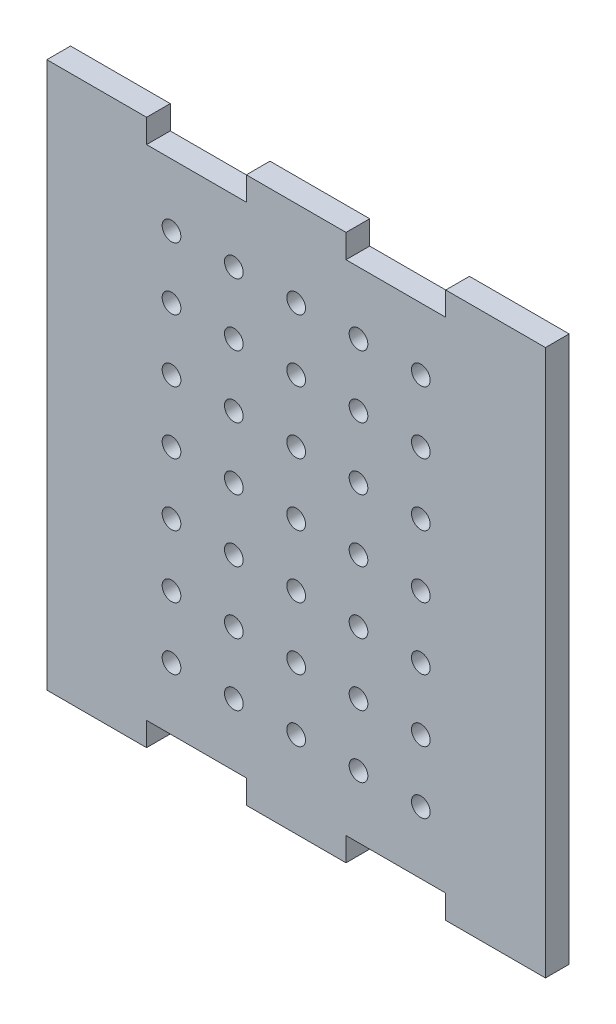
SolidWorks part; units mm, degrees
ref_plane "Front Plane" through (0, 0, 0) normal (0, 0, 1) x (1, 0, 0)
ref_plane "Top Plane" through (0, 0, 0) normal (0, 1, 0) x (1, 0, 0)
ref_plane "Right Plane" through (0, 0, 0) normal (1, 0, 0) x (0, 0, -1)
sketch "Sketch1" plane through (0, 0, 0) normal (0, 0, 1) x (1, 0, 0)
  line L0 (0, 4.826) -> (20.32, 4.826) construction
  line L1 (0, 0) -> (101.6, 0)
  line L2 (0, 0) -> (0, 111.252)
  line L3 (0, 111.252) -> (101.6, 111.252)
  line L4 (101.6, 0) -> (101.6, 111.252)
  line L5 (20.32, 0) -> (40.64, 0)
  line L6 (20.32, 0) -> (20.32, 4.826)
  line L7 (20.32, 4.826) -> (40.64, 4.826)
  line L8 (40.64, 0) -> (40.64, 4.826)
  line L9 (60.96, 0) -> (81.28, 0)
  line L10 (60.96, 0) -> (60.96, 4.826)
  line L11 (60.96, 4.826) -> (81.28, 4.826)
  line L12 (81.28, 0) -> (81.28, 4.826)
  line L13 (40.64, 4.826) -> (60.96, 4.826) construction
  line L14 (101.6, 4.826) -> (81.28, 4.826) construction
  line L15 (0, 55.626) -> (101.6, 55.626) construction
  line L16 (101.6, 106.426) -> (81.28, 106.426) construction
  line L17 (40.64, 106.426) -> (60.96, 106.426) construction
  line L18 (0, 106.426) -> (20.32, 106.426) construction
  line L19 (81.28, 111.252) -> (81.28, 106.426)
  line L20 (60.96, 106.426) -> (81.28, 106.426)
  line L21 (60.96, 111.252) -> (60.96, 106.426)
  line L22 (60.96, 111.252) -> (81.28, 111.252)
  line L23 (40.64, 111.252) -> (40.64, 106.426)
  line L24 (20.32, 106.426) -> (40.64, 106.426)
  line L25 (20.32, 111.252) -> (20.32, 106.426)
  line L26 (20.32, 111.252) -> (40.64, 111.252)
  line L27 (0, 111.252) -> (101.6, 111.252)
  line L28 (101.6, 4.826) -> (81.28, 4.826) construction
  dimension "D1" = 111.252
  dimension "D2" = 101.6
  dimension "D3" = 4.826
extrude "Boss-Extrude1" add sketch "Sketch1" along normal blind 4.826 contours L25 L3 L2 L1 L6 L7 L8 L10 L11 L12 L4 L19 L20 L21 L23 L24 region at (50.8, 55.626, 0)
sketch "Sketch2" plane through (0, 0, 4.826) normal (0, 0, 1) x (1, 0, 0)
  circle A0 centre (50.8, 68.326) radius 1.905
  circle A1 centre (63.5, 68.326) radius 1.905
  circle A2 centre (76.2, 68.326) radius 1.905
  circle A3 centre (63.5, 81.026) radius 1.905
  circle A4 centre (76.2, 81.026) radius 1.905
  circle A5 centre (63.5, 93.726) radius 1.905
  circle A6 centre (76.2, 93.726) radius 1.905
  circle A11 centre (38.1, 68.326) radius 1.905
  circle A12 centre (25.4, 68.326) radius 1.905
  circle A13 centre (38.1, 81.026) radius 1.905
  circle A14 centre (25.4, 81.026) radius 1.905
  circle A15 centre (50.8, 106.426) radius 1.905 [skipped]
  circle A16 centre (50.8, 93.726) radius 1.905 [skipped]
  circle A17 centre (50.8, 81.026) radius 1.905 [skipped]
  circle A18 centre (50.8, 119.126) radius 1.905 [skipped]
  circle A19 centre (38.1, 93.726) radius 1.905
  circle A20 centre (25.4, 93.726) radius 1.905
  circle A25 centre (50.8, 81.026) radius 1.905
  circle A26 centre (50.8, 93.726) radius 1.905
  circle A29 centre (63.5, 68.326) radius 1.905 [skipped]
  circle A30 centre (76.2, 68.326) radius 1.905 [skipped]
  circle A31 centre (63.5, 55.626) radius 1.905
  circle A32 centre (76.2, 55.626) radius 1.905
  circle A33 centre (63.5, 42.926) radius 1.905
  circle A34 centre (76.2, 42.926) radius 1.905
  circle A35 centre (63.5, 30.226) radius 1.905
  circle A36 centre (76.2, 30.226) radius 1.905
  circle A37 centre (63.5, 17.526) radius 1.905
  circle A38 centre (76.2, 17.526) radius 1.905
  circle A39 centre (38.1, 55.626) radius 1.905
  circle A40 centre (25.4, 55.626) radius 1.905
  circle A41 centre (38.1, 42.926) radius 1.905
  circle A42 centre (25.4, 42.926) radius 1.905
  circle A43 centre (25.4, 68.326) radius 1.905 [skipped]
  circle A44 centre (38.1, 68.326) radius 1.905 [skipped]
  circle A45 centre (50.8, 55.626) radius 1.905 [skipped]
  circle A46 centre (50.8, 42.926) radius 1.905 [skipped]
  circle A47 centre (50.8, 30.226) radius 1.905 [skipped]
  circle A48 centre (50.8, 17.526) radius 1.905 [skipped]
  circle A49 centre (38.1, 30.226) radius 1.905
  circle A50 centre (25.4, 30.226) radius 1.905
  circle A51 centre (38.1, 17.526) radius 1.905
  circle A52 centre (25.4, 17.526) radius 1.905
  circle A53 centre (50.8, 55.626) radius 1.905
  circle A54 centre (50.8, 42.926) radius 1.905
  circle A55 centre (50.8, 30.226) radius 1.905
  circle A56 centre (50.8, 17.526) radius 1.905
  circle A57 centre (63.5, 106.426) radius 1.905 [skipped]
  circle A58 centre (76.2, 106.426) radius 1.905 [skipped]
  circle A59 centre (63.5, 119.126) radius 1.905 [skipped]
  circle A60 centre (76.2, 119.126) radius 1.905 [skipped]
  circle A61 centre (38.1, 106.426) radius 1.905 [skipped]
  circle A62 centre (25.4, 106.426) radius 1.905 [skipped]
  circle A63 centre (38.1, 119.126) radius 1.905 [skipped]
  circle A64 centre (25.4, 119.126) radius 1.905 [skipped]
  circle A65 centre (50.8, 106.426) radius 1.905 [skipped]
  circle A66 centre (50.8, 119.126) radius 1.905 [skipped]
  dimension "D1" = 3.81
  dimension "D2" = 3
  dimension "D3" = 5
  dimension "D4" = 3
  dimension "D5" = 5
  dimension "D6" = 3
  dimension "D7" = 5
  dimension "D8" = 3
  dimension "D9" = 5
extrude "Cut-Extrude1" cut sketch "Sketch2" against normal through all
equation "\"MDF\"= 0.19in"
equation "\"PVCID\" = 2.067in"
equation "\"PVCOD\" = 2.375in"
equation "\"GenDiameter\"= 60mm"
equation "\"GenCutDiameter\" = 1.8in"
equation "\"GenCutDistance\" = 1"
equation "\"TowerHeight\" = 6in"
equation "\"TowerFrontBase\" = 3in"
equation "\"FunnelHeight\" = 1in"
equation "\"FunnelAngle\" = 20"
equation "\"TowerSideBase\" = 3in"
equation "\"TowerPanelLength\" = 2in"
equation "\"TowerPanelLeeway\" = 0.5in"
equation "\"BaseLength\" = 9in"
equation "\"BaseWidth\" = 10in"
equation "\"WheelHoleLength\" = 3.25in"
equation "\"WheelHoleWidth\" = 26mm"
equation "\"WheelHoleFromBack\" = 1.5in"
equation "\"DropLength\" = 1in"
equation "\"DropWidth\" = 8.5in"
equation "\"BumperWidth\" = 1in"
equation "\"SmallHexDiameter\" = 0.185in"
equation "\"SmallHexHeight\" = 0.701in"
equation "\"ScrewSize\" = 0.106in"
equation "\"BigHexDiameter\" = 0.251in"
equation "\"BigHexHeight\" = 0.374in"
equation "\"PCBThickness\" = 0.066in"
equation "\"ConnectorHeight\" = 0.517in"
equation "\"BoardHeight\" = 0.583in"
equation "\"UnoStackHeight\" = 1.351in"
equation "\"UnoStackWidth\" = 3.053in"
equation "\"UnoStackLength\" = 3.152in"
equation "\"HBridgeWidth\" = 1.797in"
equation "\"HBridgeLength\" = 2.236in"
equation "\"DSWidth\" = 1.820in"
equation "\"DSLength\" = 1.833in"
equation "\"StepperWidth\" = 1.799in"
equation "\"StepperLength\" = 2.248in"
equation "\"ULNWidth\" = 1.304in"
equation "\"ULNLength\" = 1.545in"
equation "\"VSwitchHeight\" = 0.392in"
equation "\"VSwitchWidth\" = 0.637in"
equation "\"VSwitchLength\" = 1.097in"
equation "\"SkateWheelDiameter\" = 80mm"
equation "\"SkateWheelThickness\" = 24mm"
equation "\"BaseDistance\" = 3in"
equation "\"DummyVar\" = 2in"
equation "\"D1@Sketch1\"=\"MDF\"*2+4in"
equation "\"D1@Boss-Extrude1\"=\"MDF\""
equation "\"D3@Sketch1\"=\"MDF\""
